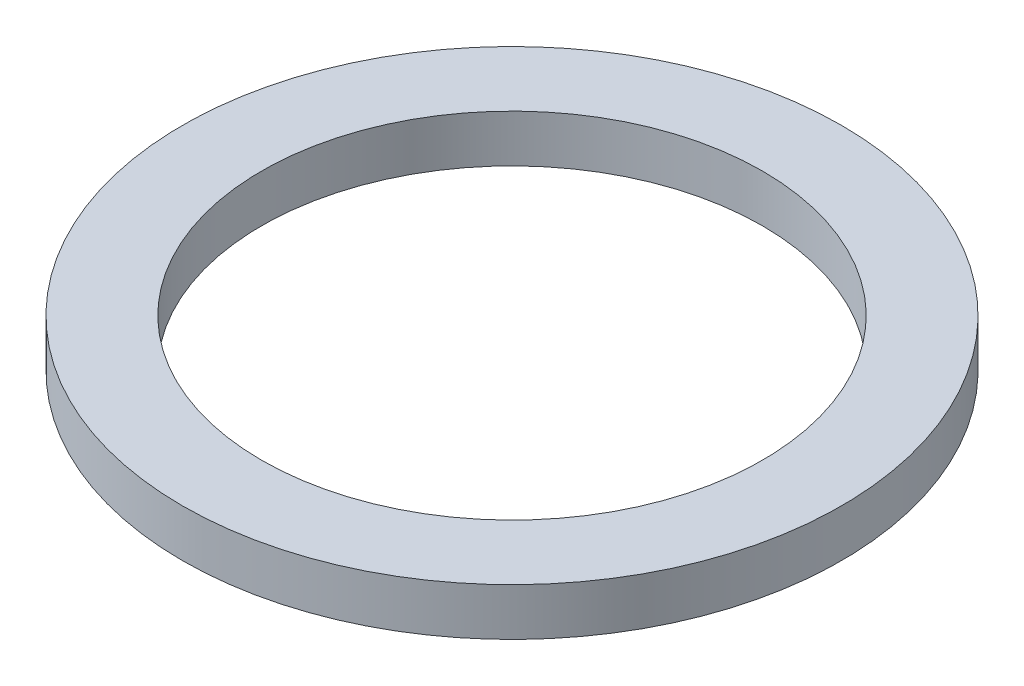
SolidWorks part; units mm, degrees
ref_plane "Front Plane" through (0, 0, 0) normal (0, 0, 1) x (1, 0, 0)
ref_plane "Top Plane" through (0, 0, 0) normal (0, 1, 0) x (1, 0, 0)
ref_plane "Right Plane" through (0, 0, 0) normal (1, 0, 0) x (0, 0, -1)
sketch "Sketch1" plane through (0, 0, 0) normal (0, 1, 0) x (1, 0, 0)
  circle A0 centre (0, 0) radius 62.5
  dimension "FLANGE_OD" = 125
extrude "Boss-Extrude1" add sketch "Sketch1" along normal blind 9
sketch "Sketch2" plane through (0, 0, 0) normal (0, 1, 0) x (1, 0, 0)
  circle A0 centre (0, 0) radius 47.5
  dimension "BORE_D" = 95
extrude "Cut-Extrude1" cut sketch "Sketch2" along normal through all
sketch "Sketch3" plane through (0, 9, 0) normal (0, 1, 0) x (1, 0, 0)
  circle A0 centre (0, 0) radius 29.1107 construction
  circle A1 centre (-29.1107, 0) radius 1.7188
  dimension "BOLT_D" = 3.4376
  dimension "BOLT_PCD" = 58.2213
extrude "Cut-Extrude2" cut sketch "Sketch3" against normal blind 6.8369 rebuild error yes
pattern_circular "CirPattern1" count 8 over 360 rebuild error yes
